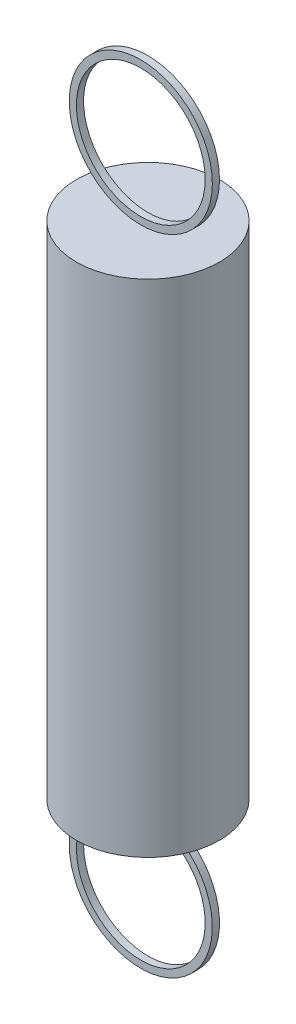
SolidWorks part; units mm, degrees
ref_plane "Front Plane" through (0, 0, 0) normal (0, 0, 1) x (1, 0, 0)
ref_plane "Top Plane" through (0, 0, 0) normal (0, 1, 0) x (1, 0, 0)
ref_plane "Right Plane" through (0, 0, 0) normal (1, 0, 0) x (0, 0, -1)
sketch "Sketch1" plane through (0, 0, 0) normal (0, 1, 0) x (1, 0, 0)
  circle A0 centre (0, 0) radius 5
  dimension "D1" = 10
extrude "Boss-Extrude1" add sketch "Sketch1" along normal blind 35 contours A0
sketch "Sketch3" plane through (0, 0, 0) normal (0, 0, 1) x (1, 0, 0)
  line L1 (5, 35) -> (-5, 35) construction
  line L2 (-5, 17.5) -> (5, 17.5) construction
  line L3 (-5, 35) -> (-5, 0) construction
  line L4 (5, 0) -> (5, 35) construction
  circle A0 centre (0, 40) radius 5
  circle A1 centre (0, 40) radius 4.5
  circle A2 centre (0, -5) radius 4.5
  circle A3 centre (0, -5) radius 5
  dimension "D1" = 0.5
  dimension "D2" = 10
extrude "Boss-Extrude2" add sketch "Sketch3" along normal blind 0.5 separate body
